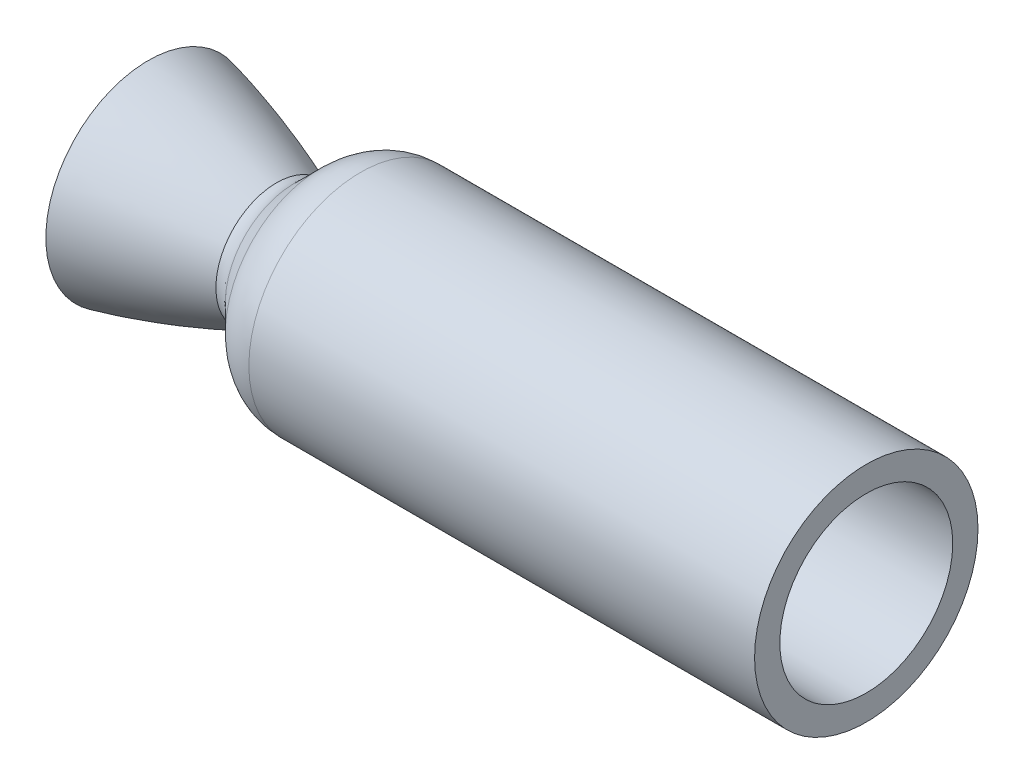
SolidWorks part; units mm, degrees
material "Hexcel AS4C (3000 Filaments)"
ref_plane "Front Plane" through (0, 0, 0) normal (0, 0, 1) x (1, 0, 0)
ref_plane "Top Plane" through (0, 0, 0) normal (0, 1, 0) x (1, 0, 0)
ref_plane "Right Plane" through (0, 0, 0) normal (1, 0, 0) x (0, 0, -1)
sketch "Sketch1" plane through (0, 0, 0) normal (0, 0, 1) x (1, 0, 0)
  line L0 (189.133, 27.386) -> (28.9492, 27.386)
  line L1 (21.8782, 24.4571) -> (13.5417, 16.1206)
  line L3 (0, 0) -> (-234.9488, 0) construction
  line L8 (189.133, 35.386) -> (28.9492, 35.386)
  line L12 (16.2213, 30.1139) -> (7.8848, 21.7775)
  line L13 (189.133, 27.386) -> (189.133, 35.386)
  line L14 (-40.127, 24.64) -> (-38.315, 32.4321)
  arc A0 (28.9492, 27.386) -> (21.8782, 24.4571) centre (28.9492, 17.386) ccw
  arc A4 (28.9492, 35.386) -> (16.2213, 30.1139) centre (28.9492, 17.386) ccw
  arc A7 (2.3482, 19.2268) -> (2.3482, 19.2268) centre (2.3482, 19.2268) cw
  arc A8 (7.8848, 21.7775) -> (2.3482, 19.2268) centre (1.6623, 28) cw construction
  arc A9 (2.3482, 19.2268) -> (7.8848, 21.7775) centre (1.6623, 28) ccw
  arc A10 (0.1069, 11.2722) -> (0, 11.5361) centre (3.1693, 12.6659) cw construction
  arc A11 (13.5417, 16.1206) -> (0.1069, 11.2722) centre (1.6623, 28) cw construction
  arc A12 (13.5417, 16.1206) -> (1.6623, 11.2) centre (1.6623, 28) cw
  arc A13 (1.6623, 11.2) -> (0, 11.5361) centre (1.6623, 15.4784) cw
  spline S0 degree 2 poles (0, 11.5361) (-19.9483, 19.9476) (-40.127, 24.64) knots 0 0 0 1 1 1 construction
  spline S1 degree 1 poles (2.3482, 19.2268) (-38.315, 32.4321) knots 0 0 1 1 construction
  spline S2 degree 2 poles (0, 11.5361) (-19.9483, 19.9476) (-40.127, 24.64) knots 0 0 0 1 1 1
  spline S3 degree 2 poles (2.3482, 19.2268) (-17.8277, 27.6653) (-38.315, 32.4321) knots 0.018494 0.018494 0.018494 1 1 1
  dimension "D1" = 10
  dimension "D4" = 16.8
  dimension "D5" = 4.2784
  dimension "D14" = 27.386
  dimension "D16" = 167.2548
  dimension "D2" = 11.2
  dimension "D6" = 45
  dimension "D7" = 24.64
  dimension "D3" = 8
revolve "Revolve1" add sketch "Sketch1" angle 360 about L3 region at (72.7189, 28.6368, 0)
equation "\"theta_t\"= 36.9009 - ( 426.271 / ( \"Aet\" + 7.00037 ) ) + ( 10026.8 / ( \"Aet\" + 7.00037 ) ^ 2 ) - ( 175410 / ( \"Aet\" + 7.00037 ) ^ 3 ) + ( ( 1.6742 * ( 10 ^ 6 ) ) / ( \"Aet\" + 7.00037 ) ^ 4 ) - ( ( 6.7643 * ( 10 ^ 6 ) ) / ( \"Aet\" + 7.00037 ) ^ 5 )"
equation "\"rt\"= 11.2"
equation "\"re\"= sqr ( \"rt\" ^ 2 * \"Aet\" )"
equation "\"Aet\"= 4.84"
equation "\"L\"= 0.8 * ( ( \"re\" / tan ( 15 ) ) - ( \"rt\" / tan ( 15 ) ) )"
equation "\"lc\"= ( \"l*\" / \"cr\" )"
equation "\"b\"= tan ( \"theta_t\" )"
equation "\"a\"= ( \"re\" - \"b\" * \"L\" - \"c\" ) / \"L\" ^ 2"
equation "\"c\"= \"rt\" * ( 1.382 - 0.382 * cos ( \"theta_t\" ) )"
equation "\"cr\"= 5.9789"
equation "\"rc\"= sqr ( \"cr\" * ( \"rt\" ^ 2 ) )"
equation "\"D14@Sketch1\"=\"rc\""
equation "\"l*\"= 1000"
equation "\"D16@Sketch1\"=\"lc\""
equation "\"th\"= 8"
equation "\"theta_cr\"= 45deg"
equation "\"theta_e\"= 5.48 + ( 134.316 / ( \"Aet\" + 1.49269 ) ) - ( 1742.02 / ( \"Aet\" + 1.49269 ) ^ 2 ) + ( 13091 / ( \"Aet\" + 1.49269 ) ^ 3 ) - ( 41929.9 / ( \"Aet\" + 1.49269 ) ^ 4 ) + ( 44445.1 / ( \"Aet\" + 1.49269 ) ^ 5 )"
equation "\"Nx\"= 0"
equation "\"Ny\"= \"c\""
equation "\"Qx\"= ( \"re\" - ( tan ( \"theta_e\" ) * \"L\" ) - \"c\" ) / ( tan ( \"theta_t\" ) - tan ( \"theta_e\" ) )"
equation "\"Qy\"= tan ( \"theta_t\" ) * \"Qx\" + \"c\""
equation "\"Ex\"= \"L\""
equation "\"Ey\"= \"re\""
equation "\"D3@Sketch1\"=\"th\""
equation "\"D2@Sketch1\"=\"rt\""
equation "\"D4@Sketch1\"=\"rt\"*1.5"
equation "\"D5@Sketch1\"=\"rt\"*0.382"
equation "\"D6@Sketch1\"=\"theta_cr\""
equation "\"D7@Sketch1\"=\"re\""
